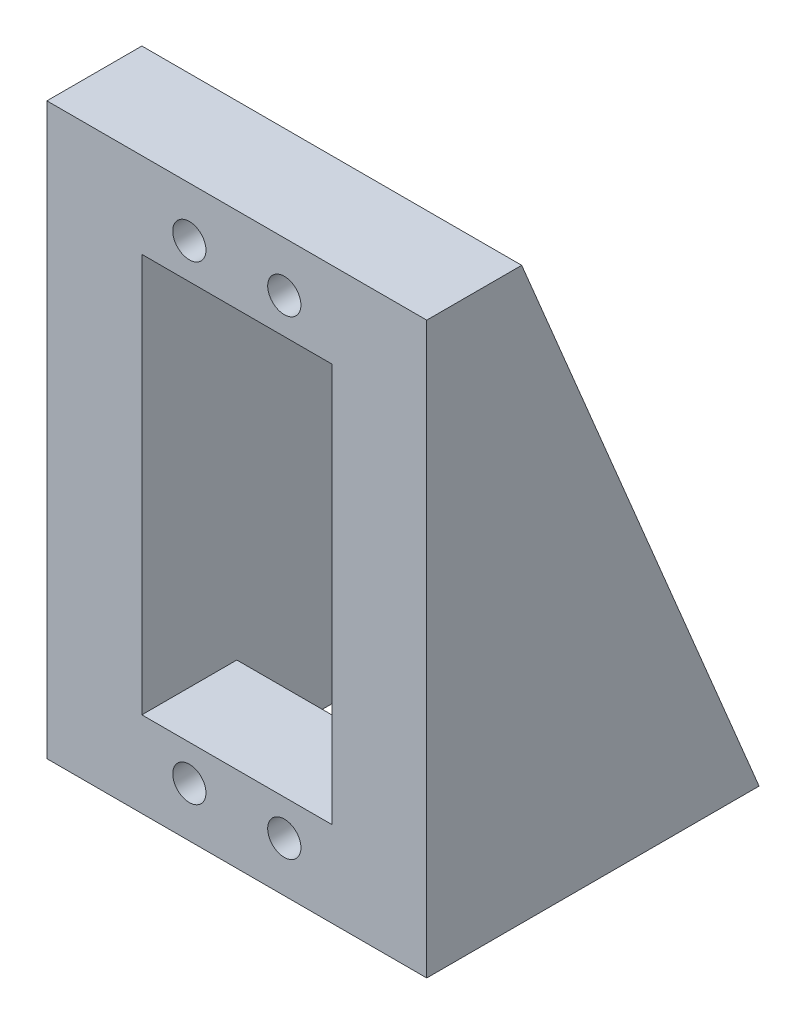
SolidWorks part; units mm, degrees
ref_plane "Front" through (0, 0, 0) normal (0, 0, 1) x (1, 0, 0)
ref_plane "Top" through (0, 0, 0) normal (0, 1, 0) x (1, 0, 0)
ref_plane "Right" through (0, 0, 0) normal (1, 0, 0) x (0, 0, -1)
sketch "Sketch2" plane through (0, 0, 0) normal (0, 0, 1) x (1, 0, 0)
  line L0 (0, 24.75) -> (0, -24.75)
  line L1 (-20, -30) -> (20, -30)
  line L2 (-20, -30) -> (-20, 30)
  line L3 (-20, 30) -> (20, 30)
  line L4 (20, -30) -> (20, 30)
  line L5 (-5, -24.75) -> (5, -24.75)
  line L6 (-5, 24.75) -> (5, 24.75)
  line L7 (-11, 21) -> (11, 21)
  line L8 (-11, 21) -> (-11, -21)
  line L9 (-11, -21) -> (11, -21)
  line L10 (11, 21) -> (11, -21)
  line L11 (-11, 21) -> (11, -21) construction
  line L12 (-11, -21) -> (11, 21) construction
  circle A0 centre (-5, 24.75) radius 1.75
  circle A1 centre (5, 24.75) radius 1.75
  circle A2 centre (-5, -24.75) radius 1.75
  circle A3 centre (5, -24.75) radius 1.75
  point P0 (0, 0)
  point P6 (0, 0)
  point P14 (0, 0)
  point P17 (0, -24.75)
  point P20 (0, 24.75)
  dimension "D1" = 42
  dimension "D2" = 22
  dimension "D3" = 40
  dimension "D4" = 60
  dimension "D5" = 9
  dimension "D6" = 9
  dimension "D7" = 49.5
  dimension "D8" = 10
  dimension "D9" = 0
extrude "Boss-Extrude1" add sketch "Sketch2" along normal blind 10 contours L1 L4 L3 L2 A3 A2 L9 L8 L7 A0 A1 L10 region at (-19.2789, 0, 0)
sketch "Sketch3" plane through (-20, 0, 0) normal (-1, 0, 0) x (0, 0, 1)
  line L0 (10, 30) -> (10, -30)
  line L1 (10, -30) -> (25, -30)
  line L2 (25, -30) -> (10, 30)
  dimension "D1" = 15
extrude "Boss-Extrude2" [suppressed] add sketch "Sketch3" against normal blind 10
sketch "Sketch4" plane through (20, 0, 0) normal (1, 0, 0) x (0, 0, -1)
  line L0 (0, -30) -> (25, -30)
  line L1 (25, -30) -> (0, 30)
  line L6 (0, -30) -> (0, 30)
  line L7 (0, 30) -> (-10, 30)
  line L8 (-10, 30) -> (-10, -30)
  line L9 (-10, -30) -> (0, -30)
  line L11 (0, 30) -> (-10, 30)
  line L13 (-10, -30) -> (0, -30)
  line L15 (-10, 30) -> (-10, -30)
  dimension "D1" = 25
  dimension "D2" = 0
extrude "Boss-Extrude3" add sketch "Sketch4" against normal blind 10
pattern_linear "LPattern1" [suppressed] count 2 spacing 30 of bodies 104
pattern_linear "LPattern2" count 2 spacing 30 along (-1, 0, 0) of "Boss-Extrude3"
sketch "Sketch5" plane through (0, -30, 0) normal (0, -1, 0) x (1, 0, 0)
  line L0 (-16, -25) -> (-16, -16.7434)
  line L1 (-20, -25) -> (-10, -25) construction
  line L2 (-16, -16.7434) -> (-16, -6.7434)
  line L3 (-16, -6.7434) -> (-16, 3.2566)
  line L4 (-20, 10) -> (-20, -25) construction
  line L5 (0, 10) -> (0, 0)
  line L6 (-20, 10) -> (20, 10) construction
  line L7 (-10, 0) -> (10, 0) construction
  circle A0 centre (-16, -16.7434) radius 1.25
  circle A1 centre (-16, 3.2566) radius 1.25
  circle A2 centre (-16, -6.7434) radius 1.25
  circle A3 centre (16, -16.7434) radius 1.25
  circle A4 centre (16, -6.7434) radius 1.25
  circle A5 centre (16, 3.2566) radius 1.25
  dimension "D2" = 10
  dimension "D4" = 4
  dimension "D1" = 8.2566
  dimension "D3" = 10
extrude "Cut-Extrude1" cut sketch "Sketch5" against normal blind 12 contours A1 | A2 | A0 | A5 | A4 | A3
